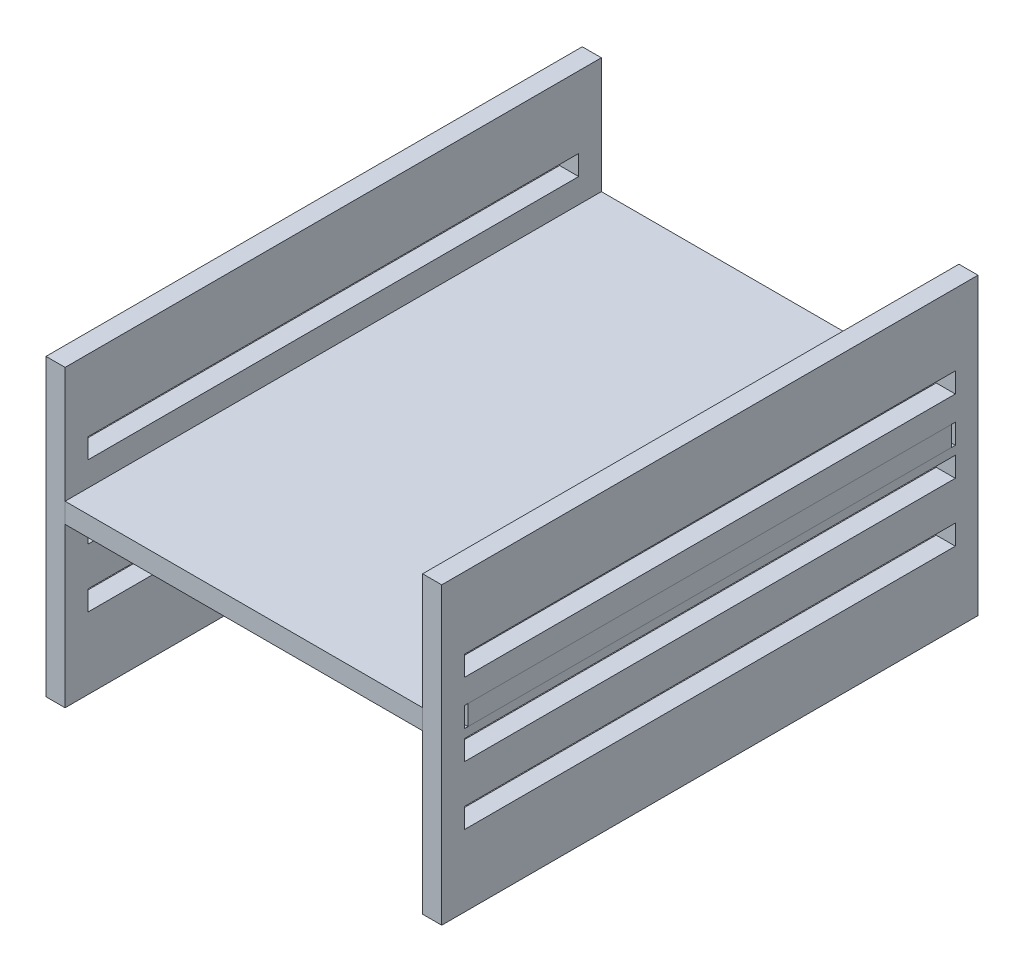
SolidWorks part; units mm, degrees
ref_plane "Front" through (0, 0, 0) normal (0, 0, 1) x (1, 0, 0)
ref_plane "Top" through (0, 0, 0) normal (0, 1, 0) x (1, 0, 0)
ref_plane "Right" through (0, 0, 0) normal (1, 0, 0) x (0, 0, -1)
sketch "Sketch1" plane through (0, 0, 0) normal (1, 0, 0) x (0, 0, -1)
  line L1 (37.5, -20.616) -> (-37.5, -20.616)
  line L2 (37.5, -20.616) -> (37.5, 20.616)
  line L3 (37.5, 20.616) -> (-37.5, 20.616)
  line L4 (-37.5, -20.616) -> (-37.5, 20.616)
  line L5 (37.5, -20.616) -> (-37.5, 20.616) construction
  line L6 (37.5, 20.616) -> (-37.5, -20.616) construction
  line L7 (34.325, -10.616) -> (-34.325, -10.616)
  line L8 (34.325, -10.616) -> (34.325, -7.816)
  line L9 (34.325, -7.816) -> (-34.325, -7.816)
  line L10 (-34.325, -10.616) -> (-34.325, -7.816)
  line L11 (34.325, -10.616) -> (-34.325, -7.816) construction
  line L12 (34.325, -7.816) -> (-34.325, -10.616) construction
  line L13 (34.325, -2.396) -> (-34.325, -2.396)
  line L14 (34.325, -2.396) -> (34.325, 0.404)
  line L15 (34.325, 0.404) -> (-34.325, 0.404)
  line L16 (-34.325, -2.396) -> (-34.325, 0.404)
  line L17 (34.325, -2.396) -> (-34.325, 0.404) construction
  line L18 (34.325, 0.404) -> (-34.325, -2.396) construction
  line L19 (34.325, 1.604) -> (-34.325, 1.604)
  line L20 (34.325, 1.604) -> (34.325, 4.404)
  line L21 (34.325, 4.404) -> (-34.325, 4.404)
  line L22 (-34.325, 1.604) -> (-34.325, 4.404)
  line L23 (34.325, 1.604) -> (-34.325, 4.404) construction
  line L24 (34.325, 4.404) -> (-34.325, 1.604) construction
  line L25 (34.325, 7.816) -> (-34.325, 7.816)
  line L26 (34.325, 7.816) -> (34.325, 10.616)
  line L27 (34.325, 10.616) -> (-34.325, 10.616)
  line L28 (-34.325, 7.816) -> (-34.325, 10.616)
  line L29 (34.325, 7.816) -> (-34.325, 10.616) construction
  line L30 (34.325, 10.616) -> (-34.325, 7.816) construction
  point P0 (0, 0)
  point P6 (0, -9.216)
  point P11 (0, 3.004)
  point P12 (0, -0.996)
  point P21 (0, 9.216)
  point P26 (0, 0)
  dimension "D1" = 75
  dimension "D2" = 3.175
  dimension "D3" = 10
  dimension "D4" = 2.8
  dimension "D5" = 5.42
  dimension "D6" = 9.42
  dimension "D7" = 10
  dimension "D8" = 15.632
extrude "Boss-Extrude1" add sketch "Sketch1" along normal blind 2.67 from offset 25
extrude "Boss-Extrude2" add sketch "Sketch1<2>" against normal blind 2.67 from offset 25 separate body offset against normal yes
sketch "Sketch1<2>" plane through (0, 0, 0) normal (1, 0, 0) x (0, 0, -1) same geometry as "Sketch1"
sketch "Sketch2" plane through (0, 1.604, 0) normal (0, 1, 0) x (1, 0, 0)
  line L0 (-27.67, 33.825) -> (-27.67, -33.825)
  line L1 (-27.67, -33.825) -> (-25, -33.825)
  line L2 (-25, -33.825) -> (-25, -37.5)
  line L3 (-25, 37.5) -> (-25, -37.5) construction
  line L4 (-25, -37.5) -> (25, -37.5)
  line L5 (25, -37.5) -> (25, -33.825)
  line L6 (25, -33.825) -> (27.67, -33.825)
  line L7 (27.67, -33.825) -> (27.67, 33.825)
  line L8 (27.67, 33.825) -> (25, 33.825)
  line L9 (25, 33.825) -> (25, 37.5)
  line L10 (25, 37.5) -> (-25, 37.5)
  line L11 (-25, 37.5) -> (-25, 33.825)
  line L12 (-25, 33.825) -> (-27.67, 33.825)
  line L13 (-27.67, 34.325) -> (-25, 34.325) construction
  line L14 (-27.67, 37.5) -> (-27.67, -37.5) construction
  line L15 (25, 37.5) -> (25, -37.5) construction
  line L16 (27.67, 37.5) -> (27.67, -37.5) construction
  line L17 (-27.67, -34.325) -> (-25, -34.325) construction
  point P26 (0, 0)
  point P31 (-27.67, 0)
  point P32 (-32.2228, -34.325)
  point P35 (24.5539, -37.5)
  point P38 (27.67, 0)
  dimension "D2" = 0.5
  dimension "D1" = 0.5
extrude "Boss-Extrude3" add sketch "Sketch2" along normal up to vertex (2.8 mm away) separate body up to point (-27.67, 4.404, -34.325)
equation "\"D1@Sketch2\"=\"D2@Sketch2\""
